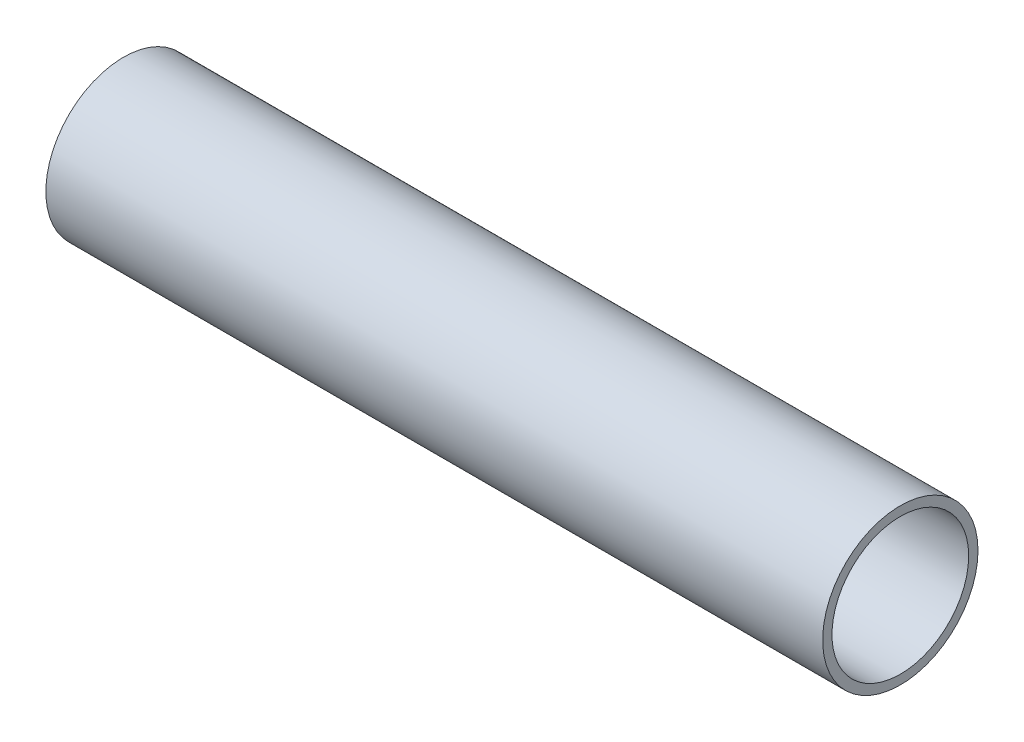
SolidWorks part; units mm, degrees
ref_plane "Спереди" through (0, 0, 0) normal (0, 0, 1) x (1, 0, 0)
ref_plane "Сверху" through (0, 0, 0) normal (0, 1, 0) x (1, 0, 0)
ref_plane "Справа" through (0, 0, 0) normal (1, 0, 0) x (0, 0, -1)
sketch "Эскиз1" plane through (0, 0, 0) normal (1, 0, 0) x (0, 0, -1)
  circle A0 centre (0, 0) radius 25
  circle A1 centre (0, 0) radius 22
  dimension "D1" = 50
  dimension "D2" = 3
extrude "Бобышка-Вытянуть1" add sketch "Эскиз1" along normal blind 250
